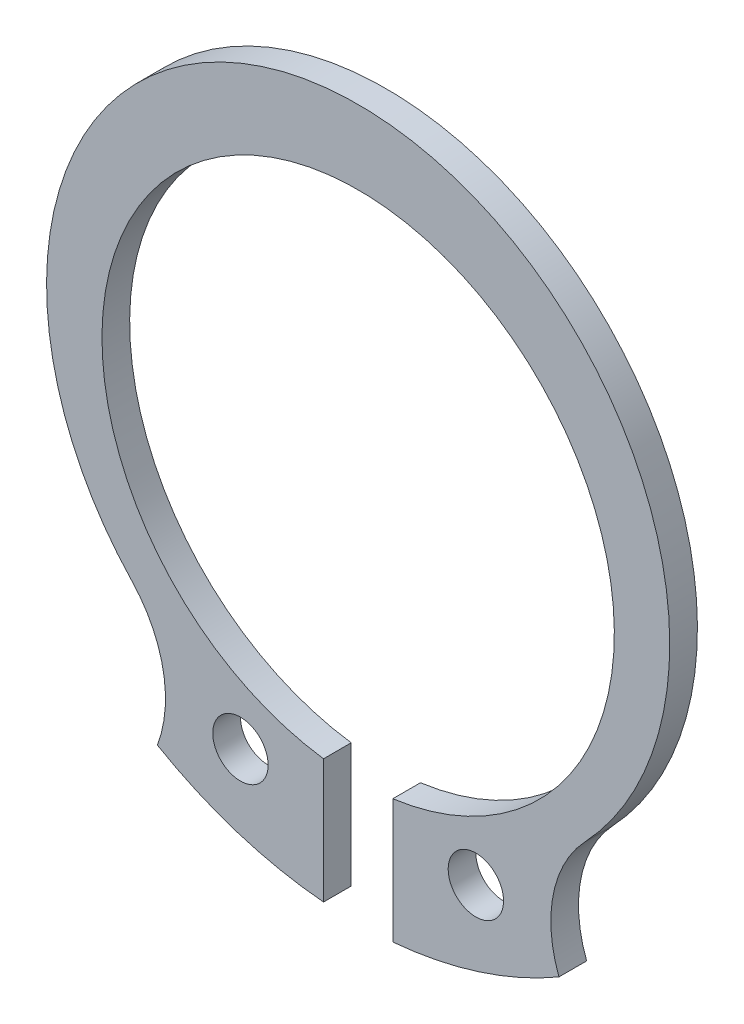
SolidWorks part; units mm, degrees
material "65Mn"
ref_plane "前视" through (0, 0, 0) normal (0, 0, 1) x (1, 0, 0)
ref_plane "上视" through (0, 0, 0) normal (0, 1, 0) x (1, 0, 0)
ref_plane "右视" through (0, 0, 0) normal (1, 0, 0) x (0, 0, -1)
sketch "尺寸草图" plane through (0, 0, 0) normal (0, 0, 1) x (1, 0, 0)
  line L0 (-11.25, 0) -> (7.25, 0) construction
  circle A0 centre (0, 0) radius 11.25
  point P5 (-10.58, 0)
  point P6 (-6.8, 0)
  point P7 (-4.8, 0)
  point P8 (-38.7, 0)
  point P9 (-27.5, 0)
  point P10 (-23, 0)
  point P11 (-8.5, 0)
  point P12 (-2.5, 0)
  point P13 (-22, 0)
  dimension "DD" = 22.5
  dimension "d" = 18.5
  dimension "c" = 0.67
  dimension "a" = 4.45
  dimension "b1" = 2.5
  dimension "b2" = 8.5
  dimension "L" = 14.5
  dimension "d1" = 2
  dimension "r2" = 4.5
  dimension "r1" = 11.2
  dimension "s" = 1
sketch "草图1" plane through (0, 0, 0) normal (0, 0, 1) x (1, 0, 0)
  line L0 (0, 0) -> (0, -7.0578) construction
  line L1 (-1.25, -9.8352) -> (-1.25, -14.3155)
  line L2 (1.25, -9.8352) -> (1.25, -14.3155)
  arc A0 (8.1831, -7.7201) -> (-8.1831, -7.7201) centre (0, 0) ccw
  arc A1 (1.25, -9.8352) -> (-1.25, -9.8352) centre (0, -0.67) ccw
  arc A2 (-7.25, -12.407) -> (-8.1831, -7.7201) centre (-11.4563, -10.8081) ccw
  arc A3 (-1.25, -14.3155) -> (-7.25, -12.407) centre (0, 0) cw
  circle A4 centre (-4.25, -11.0323) radius 1
  arc A5 (7.25, -12.407) -> (8.1831, -7.7201) centre (11.4563, -10.8081) cw
  circle A6 centre (4.25, -11.0323) radius 1
  arc A7 (1.25, -14.3155) -> (7.25, -12.407) centre (0, 0) ccw
  dimension "D1" = 22.5
  dimension "D2" = 18.5
  dimension "D7" = 4.5
  dimension "D8" = 2
  dimension "D3" = 0.67
  dimension "D5" = 2.5
  dimension "D6" = 14.5
  dimension "D4" = 4.45
  dimension "D9" = 11.2
  dimension "D10" = 8.5
extrude "基体-拉伸" add sketch "草图1" along normal blind 0.5 and the other way blind 0.5
equation "\"D1@草图1\" = \"DD@尺寸草图\""
equation "\"D2@草图1\" = \"d@尺寸草图\""
equation "\"D3@草图1\" = \"c@尺寸草图\""
equation "\"D9@草图1\" = \"r1@尺寸草图\""
equation "\"D8@草图1\" = \"d1@尺寸草图\""
equation "\"D7@草图1\" = \"r2@尺寸草图\""
equation "\"D4@草图1\" = \"a@尺寸草图\""
equation "\"D5@草图1\" = \"b1@尺寸草图\""
equation "\"D10@草图1\" = \"b2@尺寸草图\""
equation "\"D6@草图1\" = \"L@尺寸草图\""
equation "\"D1@基体-拉伸\" = \"s@尺寸草图\" / 2"
equation "\"D2@基体-拉伸\" = \"s@尺寸草图\" / 2"
